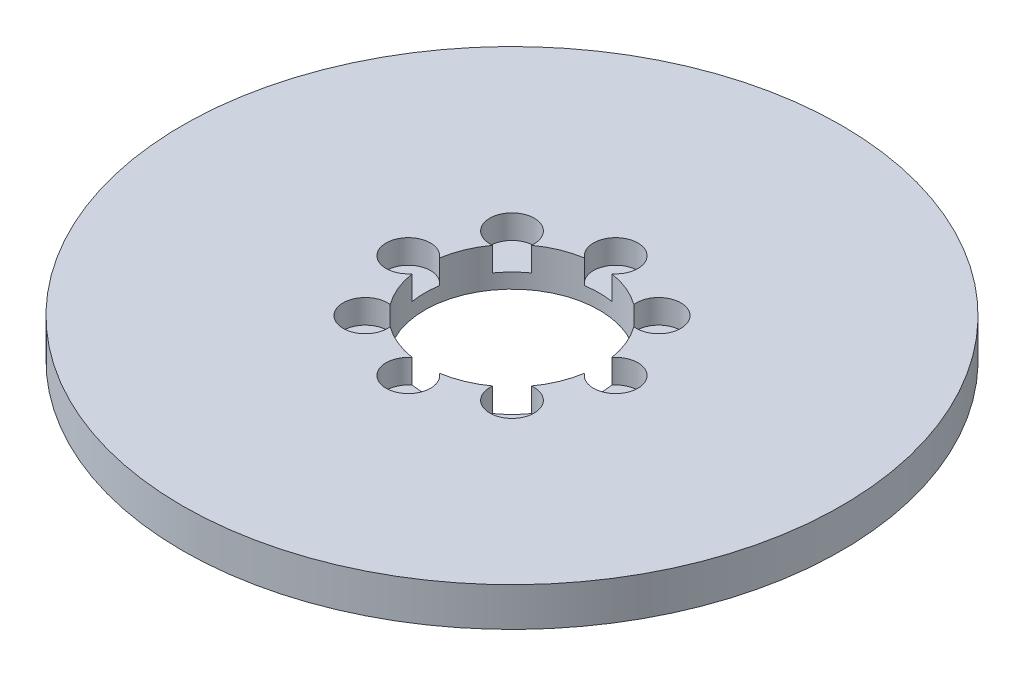
SolidWorks part; units mm, degrees
ref_plane "Front Plane" through (0, 0, 0) normal (0, 0, 1) x (1, 0, 0)
ref_plane "Top Plane" through (0, 0, 0) normal (0, 1, 0) x (1, 0, 0)
ref_plane "Right Plane" through (0, 0, 0) normal (1, 0, 0) x (0, 0, -1)
sketch "Sketch1" plane through (0, 0, 0) normal (0, 1, 0) x (1, 0, 0)
  circle A0 centre (0, 0) radius 85
  dimension "FLANGE_OD" = 170
extrude "Boss-Extrude1" add sketch "Sketch1" along normal blind 10
sketch "Sketch2" plane through (0, 0, 0) normal (0, 1, 0) x (1, 0, 0)
  circle A0 centre (0, 0) radius 22.5
  dimension "BORE_D" = 45
extrude "Cut-Extrude1" cut sketch "Sketch2" along normal through all
sketch "Sketch3" plane through (0, 10, 0) normal (0, 1, 0) x (1, 0, 0)
  circle A0 centre (0, 0) radius 26.7445 construction
  circle A1 centre (-26.7445, 0) radius 5.7259
  dimension "BOLT_D" = 11.4519
  dimension "BOLT_PCD" = 53.489
extrude "Cut-Extrude2" cut sketch "Sketch3" against normal blind 6.1703
pattern_circular "CirPattern1" count 8 over 360 about axis through (0, 0, 0) along (0, 1, 0) of "Cut-Extrude2"
